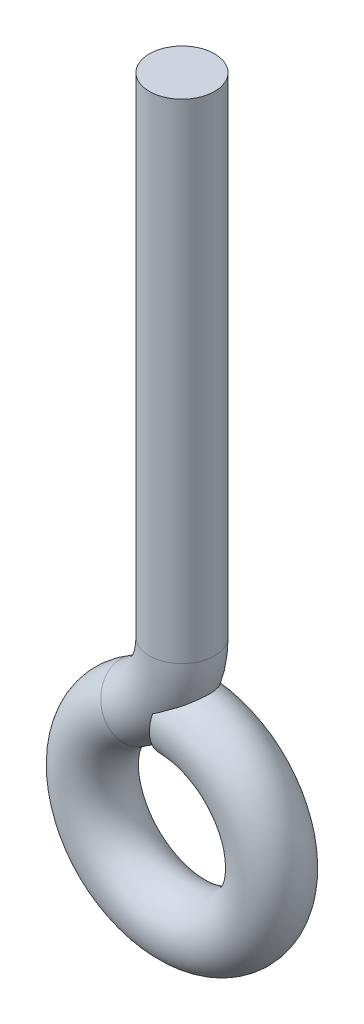
SolidWorks part; units mm, degrees
material "S235JR"
ref_plane "xy" through (0, 0, 0) normal (0, 0, 1) x (1, 0, 0)
ref_plane "xz" through (0, 0, 0) normal (0, 1, 0) x (1, 0, 0)
ref_plane "yz" through (0, 0, 0) normal (1, 0, 0) x (0, 0, -1)
ref_axis "x" through (-88.99, 0, 0) along (1, 0, 0)
ref_axis "y" through (0, 55, 0) along (0, -1, 0)
ref_axis "z" through (0, 0, -88.99) along (0, 0, 1)
sketch "Sketch1" plane through (0, 0, 0) normal (0, 0, 1) x (1, 0, 0)
  line L0 (0, 9.5263) -> (0, 39.5263)
  arc A0 (0, 5.5) -> (-2.75, 4.7631) centre (0, 0) cw
  arc A1 (-2.75, 4.7631) -> (0, 9.5263) centre (-5.5, 9.5263) ccw
  dimension "D1" = 5.5
  dimension "D2" = 30
ref_plane "Plane1" through (0, 39.5263, 0) normal (0, 1, 0) x (1, 0, 0)
sketch "Sketch2" plane through (0, 39.5263, 0) normal (0, 1, 0) x (1, 0, 0)
  circle A0 centre (0, 0) radius 2
  dimension "D1" = 4
sweep "Sweep1" add profiles "Sketch2" path "Sketch1"
